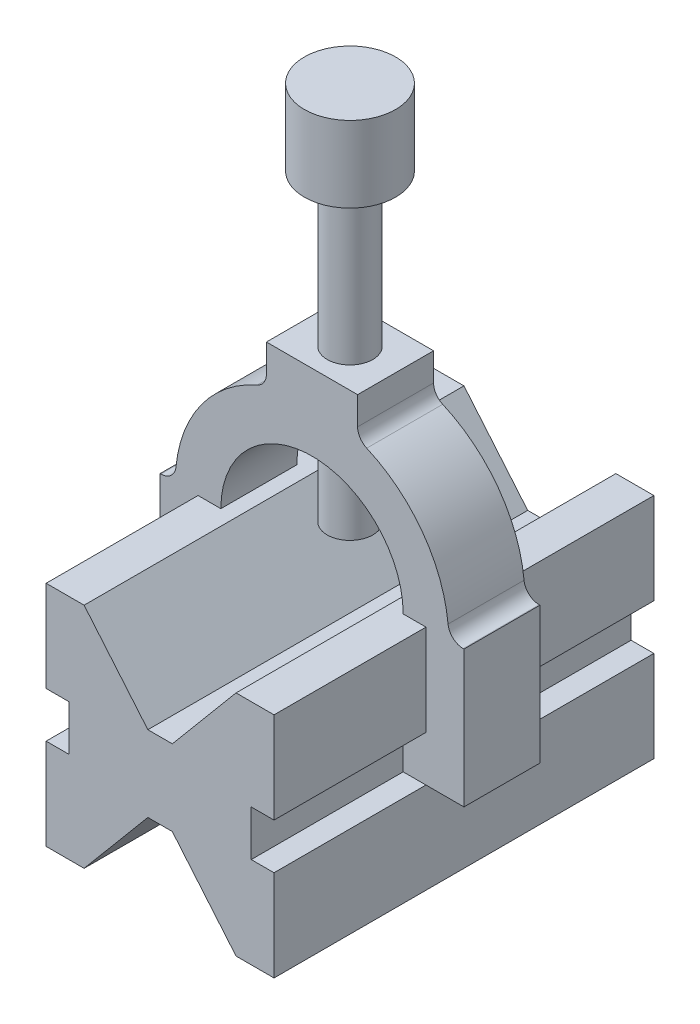
SolidWorks part; units mm, degrees
ref_plane "Front Plane" through (0, 0, 0) normal (0, 0, 1) x (1, 0, 0)
ref_plane "Top Plane" through (0, 0, 0) normal (0, 1, 0) x (1, 0, 0)
ref_plane "Right Plane" through (0, 0, 0) normal (1, 0, 0) x (0, 0, -1)
sketch "Sketch1" plane through (0, 0, 0) normal (0, 0, 1) x (1, 0, 0)
  line L0 (0, 49.3455) -> (0, -29.3455) construction
  line L2 (-67.6166, 0) -> (84.7625, 0) construction
  line L3 (-3.218, 10) -> (3.218, 10)
  line L5 (3.218, 10) -> (20, 30)
  line L6 (-3.218, 10) -> (-20, 30)
  line L7 (20, 30) -> (30, 30)
  line L8 (-20, 30) -> (-30, 30)
  line L9 (30, 30) -> (30, 6)
  line L10 (-30, 30) -> (-30, 6)
  line L11 (30, 6) -> (24, 6)
  line L12 (-30, 6) -> (-24, 6)
  line L13 (24, 6) -> (24, -6)
  line L14 (-24, 6) -> (-24, -6)
  line L15 (24, 0) -> (-24, 0)
  line L16 (30, -6) -> (24, -6)
  line L17 (30, -30) -> (30, -6)
  line L18 (20, -30) -> (30, -30)
  line L19 (3.218, -10) -> (20, -30)
  line L20 (-3.218, -10) -> (3.218, -10)
  line L21 (-3.218, -10) -> (-20, -30)
  line L22 (-20, -30) -> (-30, -30)
  line L23 (-30, -30) -> (-30, -6)
  line L24 (-30, -6) -> (-24, -6)
  point P8 (0, 10)
  point P18 (0, 0)
  dimension "D1" = 60
  dimension "D2" = 24
  dimension "D3" = 20
  dimension "D4" = 6
  dimension "D5" = 60
  dimension "D6" = 50
  dimension "D7" = 40
extrude "Boss-Extrude1" add sketch "Sketch1" along normal mid plane 100 contours L24 L23 L22 L21 L20 L19 L18 L17 L16 L13 L15 L14 | L15 L13 L11 L9 L7 L5 L3 L6 L8 L10 L12 L14 region at (0, 9.3292, 0) region at (0, -0.6708, 0)
sketch "Sketch2" plane through (0, 0, 0) normal (0, 0, 1) x (1, 0, 0)
  line L0 (30, -6) -> (24, -6) construction
  line L1 (24, 6) -> (24, -6) construction
  line L2 (30, 6) -> (24, 6) construction
  line L3 (30, -6) -> (24, -6)
  line L4 (24, 6) -> (24, -6)
  line L5 (30, 6) -> (24, 6)
  line L7 (40, -6) -> (24, -6)
  line L8 (40, -6) -> (40, 6)
  line L9 (40, 6) -> (24, 6)
  line L10 (24, -6) -> (24, 6)
  line L11 (40, -6) -> (24, 6) construction
  line L12 (40, 6) -> (24, -6) construction
  point P4 (32, 0)
  dimension "D1" = 16
extrude "Boss-Extrude2" add sketch "Sketch2" along normal mid plane 20 separate body contours L8 L9 L5 L4 L3 L7 region at (32, 0, 0)
sketch "Sketch4" plane through (0, 0, 10) normal (0, 0, 1) x (1, 0, 0)
  line L0 (30, 30) -> (30, 6) construction
  line L1 (30, 30) -> (30, 6)
  line L3 (40, 6) -> (30, 6)
  line L4 (40, -6) -> (40, 6)
  line L5 (40, 6) -> (24, 6)
  line L6 (24, 6) -> (24, -6)
  line L7 (24, -6) -> (40, -6)
  line L8 (40, -6) -> (40, 6)
  line L9 (40, 6) -> (24, 6)
  line L10 (24, 6) -> (24, -6)
  line L11 (24, -6) -> (40, -6)
  line L12 (40, 6) -> (40, 30)
  line L13 (40, 30) -> (30, 30)
  line L14 (30, 6) -> (30, 30)
  line M10 (40, 6) -> (24, 6)
  dimension "D1" = 0
extrude "Boss-Extrude4" add sketch "Sketch4" against normal up to vertex (20 mm away) contours L12 L13 L1 M10 region at (35, 18, 10) up to point (40, 6, -10)
mirror "Mirror2" about plane through (0, 0, 0) normal (1, 0, 0) of bodies 104
sketch "Sketch5" plane through (0, 0, 10) normal (0, 0, 1) x (1, 0, 0)
  line L0 (0, 0) -> (0, 42.4873) construction
  line L1 (20, 30) -> (-20, 30) construction
  line L2 (-40, 30) -> (-40, -6) construction
  line L3 (-40, -6) -> (-24, -6) construction
  line L4 (-24, -6) -> (-24, 6) construction
  line L5 (-24, 6) -> (-30, 6) construction
  line L6 (-30, 6) -> (-30, 30) construction
  line L7 (-30, 30) -> (-40, 30) construction
  line L8 (40, -6) -> (40, 30) construction
  line L9 (40, 30) -> (30, 30) construction
  line L10 (30, 30) -> (30, 6) construction
  line L11 (30, 6) -> (24, 6) construction
  line L12 (24, 6) -> (24, -6) construction
  line L13 (24, -6) -> (40, -6) construction
  line L14 (-40, 30) -> (-40, -6)
  line L15 (-40, -6) -> (-24, -6)
  line L16 (-24, -6) -> (-24, 6)
  line L17 (-24, 6) -> (-30, 6)
  line L18 (-30, 6) -> (-30, 30)
  line L19 (-30, 30) -> (-40, 30)
  line L20 (40, -6) -> (40, 30)
  line L21 (-24, -6) -> (-30, -6)
  line L22 (-30, -6) -> (-30, -30)
  line L23 (-30, -30) -> (-20, -30)
  line L24 (-20, -30) -> (-3.218, -10)
  line L25 (-3.218, -10) -> (3.218, -10)
  line L26 (3.218, -10) -> (20, -30)
  line L27 (20, -30) -> (30, -30)
  line L28 (30, -30) -> (30, -6)
  line L29 (30, -6) -> (24, -6)
  line L30 (24, -6) -> (24, 6)
  line L31 (24, 6) -> (30, 6)
  line L32 (30, 6) -> (30, 30)
  line L33 (30, 30) -> (20, 30)
  line L34 (20, 30) -> (3.218, 10)
  line L35 (3.218, 10) -> (-3.218, 10)
  line L36 (-3.218, 10) -> (-20, 30)
  line L37 (-20, 30) -> (-30, 30)
  line L38 (-30, 30) -> (-30, 6)
  line L39 (-30, 6) -> (-24, 6)
  line L40 (-24, 6) -> (-24, -6)
  line L41 (-24, -6) -> (-30, -6)
  line L42 (-30, -6) -> (-30, -30)
  line L43 (-30, -30) -> (-20, -30)
  line L44 (-20, -30) -> (-3.218, -10)
  line L45 (-3.218, -10) -> (3.218, -10)
  line L46 (3.218, -10) -> (20, -30)
  line L47 (20, -30) -> (30, -30)
  line L48 (30, -30) -> (30, -6)
  line L49 (30, -6) -> (24, -6)
  line L50 (24, -6) -> (24, 6)
  line L51 (24, 6) -> (30, 6)
  line L52 (30, 6) -> (30, 30)
  line L53 (30, 30) -> (20, 30)
  line L54 (20, 30) -> (3.218, 10)
  line L55 (3.218, 10) -> (-3.218, 10)
  line L56 (-3.218, 10) -> (-20, 30)
  line L57 (-20, 30) -> (-30, 30)
  line L58 (-30, 30) -> (-30, 6)
  line L59 (-30, 6) -> (-24, 6)
  line L60 (-24, 6) -> (-24, -6)
  line L61 (40, 30) -> (30, 30)
  line L62 (30, 30) -> (30, 6)
  line L63 (30, 6) -> (24, 6)
  line L64 (24, 6) -> (24, -6)
  line L65 (24, -6) -> (40, -6)
  line L66 (24, 30) -> (36, 30)
  line L67 (-36, 30) -> (-24, 30)
  line L70 (12, 63.9411) -> (12, 74)
  line L71 (12, 74) -> (-12, 74)
  line L72 (-12, 63.9411) -> (-12, 74)
  arc A0 (24, 30) -> (-24, 30) centre (0, 30) ccw
  arc A1 (36, 30) -> (12, 63.9411) centre (0, 30) ccw
  arc A2 (-12, 63.9411) -> (-36, 30) centre (0, 30) ccw
  dimension "D2" = 48
  dimension "D3" = 72
  dimension "D4" = 80
  dimension "D1" = 0
  dimension "D5" = 24
extrude "Boss-Extrude5" add sketch "Sketch5" against normal up to vertex (20 mm away) contours L72 A2 L19 L57 A0 L53 L61 A1 L70 L71 region at (-28.7049, 50.2974, 10) up to point (40, 30, -10)
combine bodies "Combine2" operation type add bodies to combine 106 105
sketch "Sketch6" plane through (0, 74, 0) normal (0, 1, 0) x (1, 0, 0)
  line L4 (-12, -10) -> (12, -10)
  line L5 (12, -10) -> (12, 10)
  line L6 (12, 10) -> (-12, 10)
  line L7 (-12, 10) -> (-12, -10)
  line L8 (-12, -10) -> (12, -10)
  line L9 (12, -10) -> (12, 10)
  line L10 (12, 10) -> (-12, 10)
  line L11 (-12, 10) -> (-12, -10)
  circle A0 centre (0, 0) radius 6
  dimension "D2" = 12
  dimension "D1" = 0
extrude "Cut-Extrude1" cut sketch "Sketch6" against normal up to surface (20 mm away) contours A0 up to face at (0, 42, 0)
fillet "Fillet1" radius 4 4 edges at (12, 63.9411, 0) (-12, 63.9411, 0) (36, 30, 0) (-36, 30, 0)
sketch "Sketch7" plane through (0, 74, 0) normal (0, 1, 0) x (1, 0, 0)
  line L4 (-12, -10) -> (12, -10)
  line L5 (12, -10) -> (12, 10)
  line L6 (12, 10) -> (-12, 10)
  line L7 (-12, 10) -> (-12, -10)
  line L8 (-12, -10) -> (12, -10)
  line L9 (12, -10) -> (12, 10)
  line L10 (12, 10) -> (-12, 10)
  line L11 (-12, 10) -> (-12, -10)
  circle A0 centre (0, 0) radius 6 construction
  circle A1 centre (0, 0) radius 6
  circle M6 centre (0, 0) radius 6
  line M7 (-12, -10) -> (12, -10)
  line M8 (12, -10) -> (12, 10)
  line M9 (12, 10) -> (-12, 10)
  line M10 (-12, 10) -> (-12, -10)
  dimension "D1" = 0
extrude "Boss-Extrude6" add sketch "Sketch7" along normal blind 40 and the other way blind 40 separate body contours M10 M7 M8 M9 M6 | L8 L9 L10 L11 region at (-11.6876, 74, 0)
sketch "Sketch8" plane through (0, 114, 0) normal (0, 1, 0) x (1, 0, 0)
  circle A0 centre (0, 0) radius 12
  circle A1 centre (0, 0) radius 6
  circle A2 centre (0, 0) radius 6
  circle M3 centre (0, 0) radius 6
  dimension "D2" = 12
  dimension "D1" = 0
extrude "Boss-Extrude7" add sketch "Sketch8" along normal blind 20 contours M3 | A0 M3 region at (-11.6606, 114, 0) region at (0, 114, 0)
